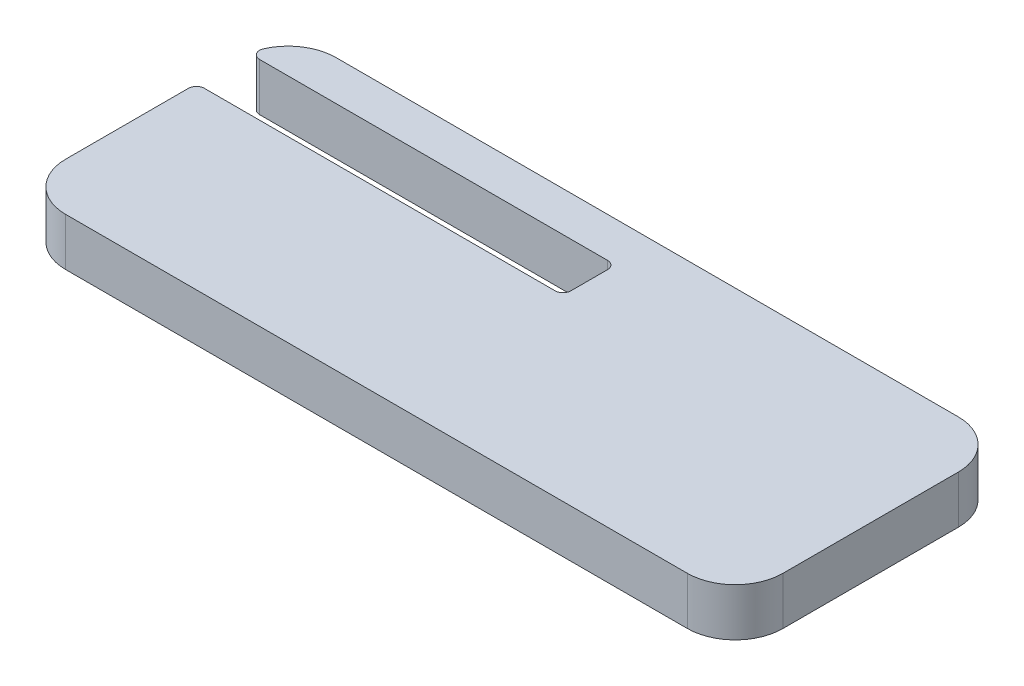
SolidWorks part; units mm, degrees
ref_plane "Alzado" through (0, 0, 0) normal (0, 0, 1) x (1, 0, 0)
ref_plane "Planta" through (0, 0, 0) normal (0, 1, 0) x (1, 0, 0)
ref_plane "Vista lateral" through (0, 0, 0) normal (1, 0, 0) x (0, 0, -1)
sketch "Croquis1" plane through (0, 0, 0) normal (0, 1, 0) x (1, 0, 0)
  line L5 (-22.5, 9.9298) -> (22.5, 9.9298)
  line L6 (-22.5, 9.9298) -> (-22.5, -7.0702)
  line L7 (-22.5, -7.0702) -> (22.5, -7.0702)
  line L8 (22.5, 9.9298) -> (22.5, -7.0702)
  dimension "D1" = 9.9298
  dimension "D2" = 22.5
  dimension "D3" = 17
  dimension "D4" = 45
extrude "Saliente-Extruir1" add sketch "Croquis1" along normal blind 3
sketch "Croquis2" plane through (0, 3, 0) normal (0, 1, 0) x (1, 0, 0)
  line L0 (-22.5, 9.9298) -> (-22.5, -7.0702) construction
  line L1 (-22.5, 7.4298) -> (0.5, 7.4298)
  line L2 (-22.5, 7.4298) -> (-22.5, 4.1298)
  line L3 (-22.5, 4.1298) -> (0.5, 4.1298)
  line L4 (0.5, 7.4298) -> (0.5, 4.1298)
  line L6 (22.5, 9.9298) -> (-22.5, 9.9298) construction
  dimension "D1" = 23
  dimension "D2" = 2.5
  dimension "D3" = 3.3
extrude "Cortar-Extruir1" cut sketch "Croquis2" against normal up to surface (3 mm away) up to face at (0, 0, -1.4298)
fillet "Redondeo1" radius 3 4 edges at (-22.5, 1.5, 7.0702) (-22.5, 1.5, -9.9298) (22.5, 1.5, 7.0702) (22.5, 1.5, -9.9298)
fillet "Redondeo4" radius 0.5 4 edges at (-22.5, 1.5, -4.1298) (0.5, 1.5, -4.1298) (0.5, 1.5, -7.4298) (-22.5, 1.5, -7.4298)
